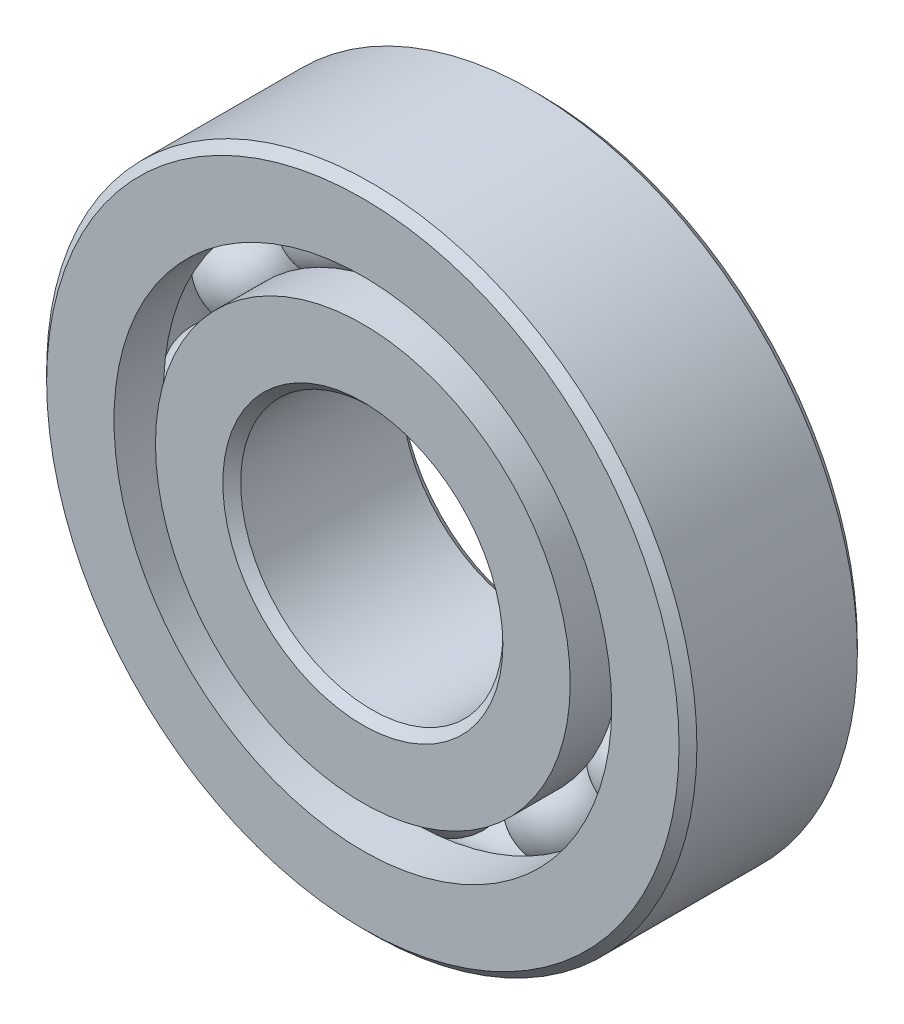
SolidWorks part; units mm, degrees
ref_plane "Front Plane" through (0, 0, 0) normal (0, 0, 1) x (1, 0, 0)
ref_plane "Top Plane" through (0, 0, 0) normal (0, 1, 0) x (1, 0, 0)
ref_plane "Right Plane" through (0, 0, 0) normal (1, 0, 0) x (0, 0, -1)
sketch "Sketch1" plane through (0, 0, 0) normal (1, 0, 0) x (0, 0, -1)
  line L0 (-8.5, 0) -> (8.5, 0) construction
  line L1 (0, 31) -> (0, -31) construction
  line L2 (7.65, 31) -> (-7.65, 31)
  line L3 (-7.65, 31) -> (-8.5, 30.15)
  line L4 (-8.5, 30.15) -> (-8.5, 23.728)
  line L5 (-8.5, 23.728) -> (-3.7778, 23.728)
  line L6 (8.5, 23.728) -> (3.7778, 23.728)
  line L7 (8.5, 30.15) -> (8.5, 23.728)
  line L8 (7.65, 31) -> (8.5, 30.15)
  line L9 (0, 31) -> (0, 21.75) construction
  line L10 (0, 21.75) -> (0, 12.5) construction
  arc A0 (-3.7778, 23.728) -> (3.7778, 23.728) centre (0, 21.75) cw
  point P14 (0, 12.5)
  dimension "Width" = 17
  dimension "OD" = 62
  dimension "D1" = 45
  dimension "D2" = 0.85
  dimension "Shaft Dia" = 25
  dimension "D3" = 7.5556
  dimension "D4" = 1.978
revolve "Revolve1" add sketch "Sketch1" angle 360 about L0
sketch "Sketch3" plane through (0, 0, 0) normal (1, 0, 0) x (0, 0, -1)
  line L0 (-8.5, 19.772) -> (-3.7778, 19.772)
  line L1 (0, 31) -> (0, -31) construction
  line L2 (-8.5, 30.15) -> (-8.5, 23.728) construction
  line L3 (-8.5, 19.772) -> (-8.5, 13.35)
  line L4 (-7.65, 31) -> (-8.5, 30.15) construction
  line L5 (-8.5, 13.35) -> (-7.65, 12.5)
  line L6 (-7.65, 12.5) -> (7.65, 12.5)
  line L7 (7.65, 31) -> (7.65, -31) construction
  line L8 (7.65, 12.5) -> (8.5, 13.35)
  line L9 (8.5, -30.15) -> (8.5, 30.15) construction
  line L10 (8.5, 13.35) -> (8.5, 19.772)
  line L11 (8.5, 19.772) -> (3.7778, 19.772)
  line L13 (7.65, 31) -> (8.5, 30.15) construction
  arc A0 (3.7778, 23.728) -> (-3.7778, 23.728) centre (0, 21.75) ccw construction
  arc A1 (3.7778, 19.772) -> (-3.7778, 19.772) centre (0, 21.75) cw
revolve "Revolve3" add sketch "Sketch3" angle 360 about L0
sketch "Sketch4" plane through (0, 0, 0) normal (1, 0, 0) x (0, 0, -1)
  line L0 (-4.2643, 21.75) -> (4.2643, 21.75)
  arc A2 (-4.2643, 21.75) -> (4.2643, 21.75) centre (0, 21.75) cw
  arc A3 (3.7778, 23.728) -> (-3.7778, 23.728) centre (0, 21.75) ccw construction
revolve "Revolve4" add sketch "Sketch4" angle 360 about L0
ref_axis "Axis1" through (0, 0, -8.5) along (0, 0, 1)
pattern_circular "CirPattern1" count 12 over 360 about axis through (0, 0, -8.5) along (0, 0, 1) of bodies 104
sketch "Sketch5" plane through (0, 0, 0) normal (1, 0, 0) x (0, 0, -1)
  line L0 (-8.5, 23.728) -> (-3.7778, 23.728) construction
  line L1 (-8.075, 23.728) -> (-4.2643, 23.728)
  line L2 (-8.075, 23.728) -> (-8.075, 19.772)
  line L3 (-8.075, 19.772) -> (-4.2643, 19.772)
  line L4 (-4.2643, 23.728) -> (-4.2643, 19.772)
  line L5 (-8.5, 19.772) -> (-3.7778, 19.772) construction
  line L6 (8.5, 23.728) -> (3.7778, 23.728) construction
  line L7 (8.075, 23.728) -> (4.2643, 23.728)
  line L8 (8.075, 23.728) -> (8.075, 19.772)
  line L9 (8.075, 19.772) -> (4.2643, 19.772)
  line L10 (4.2643, 23.728) -> (4.2643, 19.772)
  line L11 (8.5, 19.772) -> (3.7778, 19.772) construction
  line L12 (-7.65, 31) -> (-8.5, 30.15) construction
  point P18 (-8.075, 30.575)
equation "\"D2@Sketch1\" = \"Width@Sketch1\"*.05"
equation "\"D3@Sketch1\" = \"Width@Sketch1\"/2.25"
equation "\"D4@Sketch1\" = (((\"OD@Sketch1\"-\"Width@Sketch1\")/2)/3.25)/3.5"
equation "\"D2@CirPattern1\" = 360/\"Balls@CirPattern1\""
